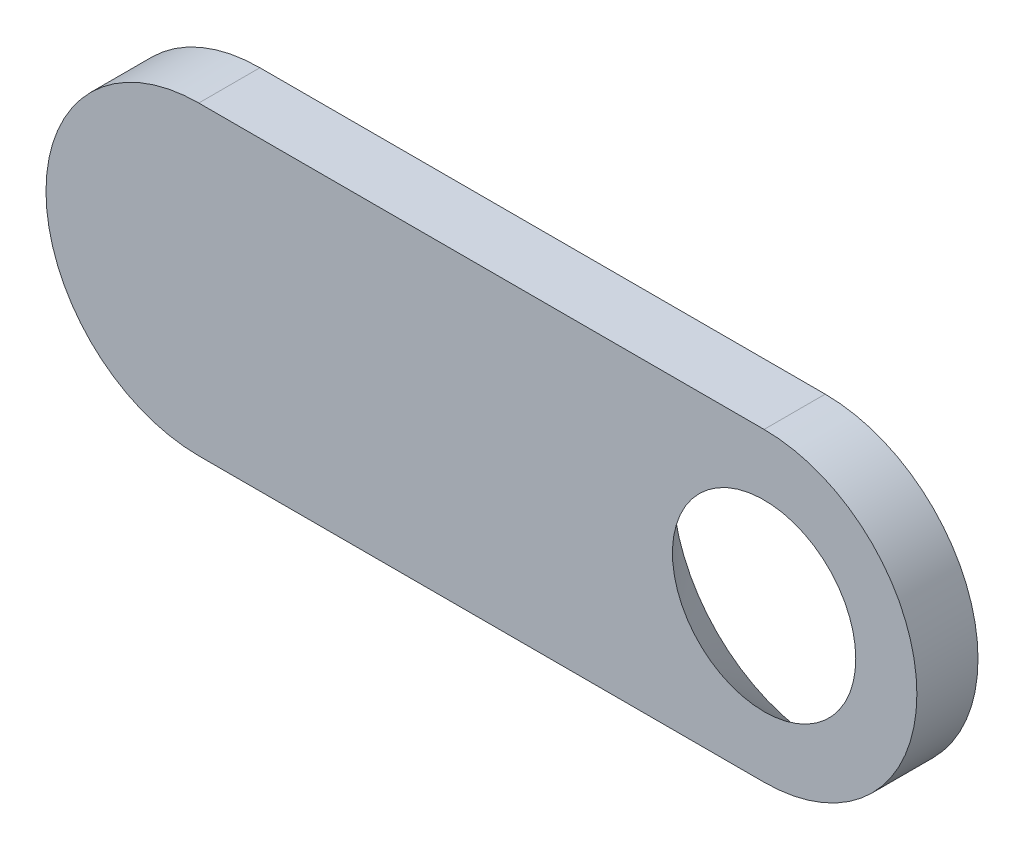
SolidWorks part; units mm, degrees
material "Delrin 2700 NC010, Low Viscosity Acetal Copolymer (SS)"
ref_plane "Front Plane" through (0, 0, 0) normal (0, 0, 1) x (1, 0, 0)
ref_plane "Top Plane" through (0, 0, 0) normal (0, 1, 0) x (1, 0, 0)
ref_plane "Right Plane" through (0, 0, 0) normal (1, 0, 0) x (0, 0, -1)
sketch "Sketch1" plane through (0, 0, 0) normal (0, 0, 1) x (1, 0, 0)
  line L0 (34, -5) -> (15.5, -5)
  line L1 (0, 0) -> (10.5, 0) construction
  line L2 (15.5, 5) -> (34, 5)
  circle A0 centre (34, 0) radius 3
  arc A1 (34, -5) -> (34, 5) centre (34, 0) ccw
  arc A2 (15.5, 5) -> (15.5, -5) centre (15.5, 0) ccw
  dimension "D2" = 6
  dimension "D3" = 10
  dimension "D1" = 34
  dimension "D4" = 10.5
extrude "Boss-Extrude1" add sketch "Sketch1" along normal blind 2
chamfer "Chamfer1" distance 2 angle 45 1 edges at (37, 0, 0)
